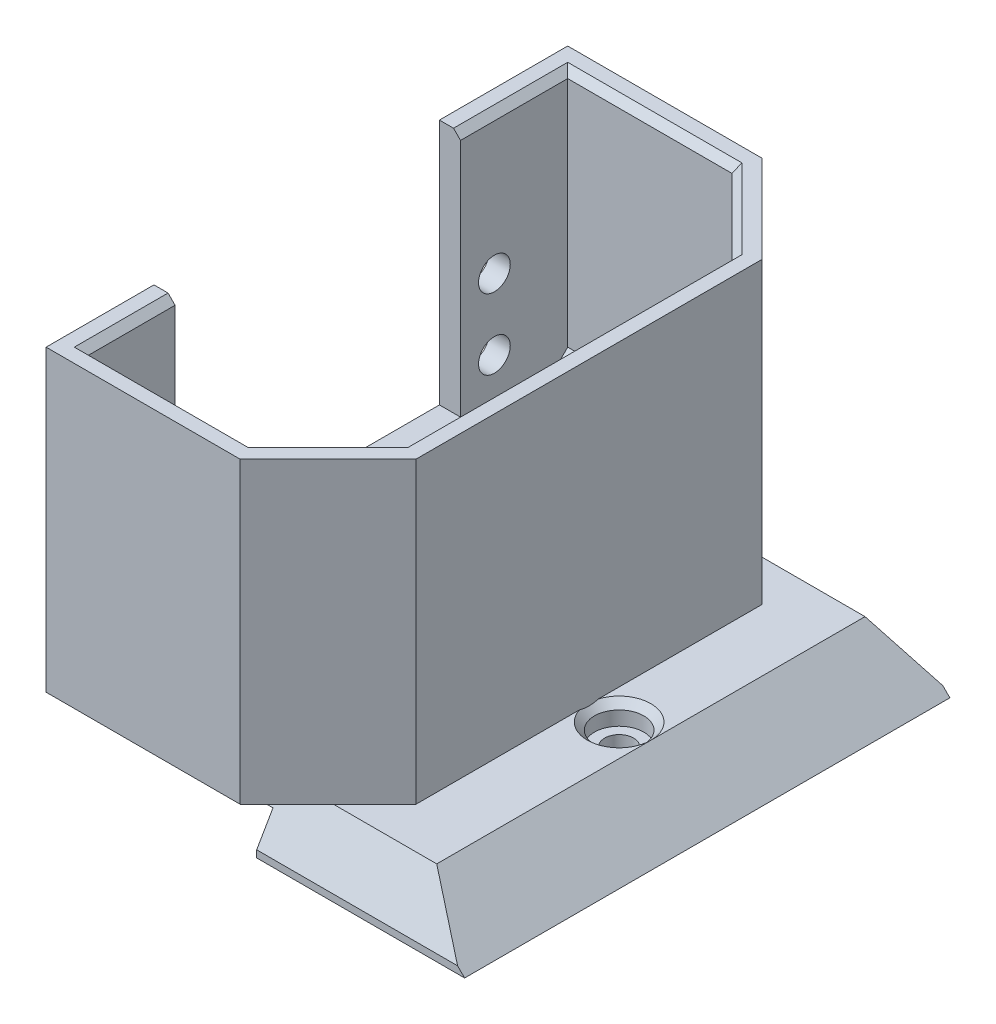
SolidWorks part; units mm, degrees
material "ABS"
ref_plane "Front Plane" through (0, 0, 0) normal (0, 0, 1) x (1, 0, 0)
ref_plane "Top Plane" through (0, 0, 0) normal (0, 1, 0) x (1, 0, 0)
ref_plane "Right Plane" through (0, 0, 0) normal (1, 0, 0) x (0, 0, -1)
sketch "Sketch1" plane through (0, 0, 0) normal (0, 1, 0) x (1, 0, 0)
  line L1 (-20, 35) -> (7.5426, 35)
  line L2 (-20, 35) -> (-20, -39)
  line L3 (-20, -39) -> (7.5426, -39)
  line L4 (20, 22.5426) -> (20, -26.5426)
  line L8 (7.5426, 35) -> (20, 22.5426)
  line L9 (7.5426, -39) -> (20, -26.5426)
  line L10 (20, 18.3) -> (3.3, 35) construction
  dimension "D4" = 20
  dimension "D5" = 3
  dimension "D3" = 16.7
  dimension "D2" = 35
  dimension "D6" = 74
  dimension "D1" = 40
extrude "Main Face Extrude" add sketch "Sketch1" along normal blind 7.4
sketch "Sketch3" plane through (0, 7.4, 0) normal (0, 1, 0) x (1, 0, 0)
  line L4 (-20, 35) -> (-20, -39)
  line L5 (-20, -39) -> (7.5426, -39)
  line L6 (20, -26.5426) -> (20, 22.5426)
  line L7 (7.5426, 35) -> (-20, 35)
  line L8 (-20, 35) -> (-20, -39)
  line L9 (-20, -39) -> (7.5426, -39)
  line L10 (20, -26.5426) -> (20, 22.5426)
  line L11 (7.5426, 35) -> (-20, 35)
  line L12 (-17, 32) -> (-17, -36)
  line L13 (-17, -36) -> (6.3, -36)
  line L14 (6.3, -36) -> (17, -25.3)
  line L15 (17, -25.3) -> (17, 21.3)
  line L16 (17, 21.3) -> (6.3, 32)
  line L17 (6.3, 32) -> (-17, 32)
  line L18 (7.5426, -39) -> (20, -26.5426)
  line L19 (7.5426, -39) -> (20, -26.5426)
  line L20 (20, 22.5426) -> (7.5426, 35)
  line L21 (20, 22.5426) -> (7.5426, 35)
  dimension "D1" = 0
  dimension "D2" = 3
extrude "Main Walls Extrude" add sketch "Sketch3" along normal blind 35
chamfer "Main Walls Lower Chamfer" distance 1 angle 45 5 edges at (-5.35, 7.4, 36) (11.65, 7.4, 30.65) (17, 7.4, 2) (11.65, 7.4, -26.65) (-5.35, 7.4, -32)
chamfer "Main Walls Entry Chamfer" distance 1 angle 45 6 edges at (-5.35, 42.4, 36) (11.65, 42.4, 30.65) (17, 42.4, 2) (11.65, 42.4, -26.65) (-17, 42.4, 2) (-5.35, 42.4, -32)
sketch "Sketch4" plane through (0, 42.4, 0) normal (0, 1, 0) x (1, 0, 0)
  line L0 (-17, 32) -> (-17, -36) construction
  line L1 (-17, 16.8) -> (-20, 16.8)
  line L2 (-17, 16.8) -> (-17, -23.7)
  line L3 (-17, -23.7) -> (-20, -23.7)
  line L4 (-20, 16.8) -> (-20, -23.7)
  line L5 (-20, 35) -> (-20, -39) construction
  point P8 (-17, -3.45)
  dimension "D1" = 40.5
  dimension "D2" = 3.45
extrude "Servo Mount Cut" cut sketch "Sketch4" against normal up to surface (35 mm away) up to face at (1.6286, 7.4, 2)
sketch "Sketch5" plane through (-20, 0, 0) normal (-1, 0, 0) x (0, 0, 1)
  line L2 (-21.6, 22.65) -> (-16.8, 22.65) construction
  line L3 (-16.8, 7.4) -> (-16.8, 42.4) construction
  line L4 (28.5, 22.65) -> (23.7, 22.65) construction
  line L5 (23.7, 7.4) -> (23.7, 42.4) construction
  line L6 (25.3, 7.4) -> (-21.3, 7.4) construction
  circle A0 centre (-21.6, 22.65) radius 2.25
  circle A1 centre (-21.6, 12.65) radius 2.25
  circle A2 centre (28.5, 22.65) radius 2.25
  circle A3 centre (28.5, 12.65) radius 2.25
  dimension "D1" = 4.5
  dimension "D2" = 10
  dimension "D3" = 50.1
  dimension "D4" = 5.25
extrude "Servo Mount Holes" cut sketch "Sketch5" against normal up to next
sketch "Sketch8" plane through (-20, 0, 0) normal (-1, 0, 0) x (0, 0, 1)
  line L0 (-28.3812, 0) -> (-32.4226, -7)
  line L1 (-35, 0) -> (39, 0) construction
  line L3 (-32.4226, -8) -> (36.4226, -8)
  line L5 (36.4226, -7) -> (32.3812, 0)
  line L6 (32.3812, 0) -> (-28.3812, 0)
  line L7 (2, -8) -> (2, 0) construction
  line L8 (-32.4226, -8) -> (-32.4226, -7)
  line L9 (36.4226, -8) -> (36.4226, -7)
  line L11 (-33, -8) -> (-32.4226, -8) construction
  line L12 (-32.4226, -7) -> (-33, -8) construction
  line L13 (36.4226, -8) -> (37, -8) construction
  line L14 (37, -8) -> (36.4226, -7) construction
  point P12 (2, 0)
  dimension "D1" = 60
  dimension "D2" = 8
  dimension "D3" = 1
  dimension "D4" = 70
extrude "Mount Dovetail" add sketch "Sketch8" against normal blind 56.8
chamfer "Mount Dovetail Chamfer" distance 8 angle 45 1 edges at (36.8, 0, 2)
sketch "Sketch9" plane through (0, -8, 0) normal (0, -1, 0) x (1, 0, 0)
  line L0 (36.8, -32.4226) -> (-20, -32.4226) construction
  line L1 (-20, 36.4226) -> (7.3, 36.4226)
  line L2 (-20, 36.4226) -> (-20, -32.4226)
  line L3 (-20, -32.4226) -> (7.3, -32.4226)
  line L4 (7.3, 36.4226) -> (7.3, -32.4226)
  dimension "D1" = 27.3
extrude "Dovetail Offset Cut" cut sketch "Sketch9" against normal blind 5
sketch "Sketch10" plane through (0, 0, 0) normal (0, 1, 0) x (1, 0, 0)
  line L0 (36.8, 32.4226) -> (36.8, -36.4226) construction
  line L1 (36.8, -2) -> (24.3, -2) construction
  circle A0 centre (24.3, -2) radius 2.05
  dimension "D2" = 4.1
  dimension "D1" = 12.5
extrude "Mount Screw Hole" cut sketch "Sketch10" against normal through all
sketch "Sketch11" plane through (0, 0, 0) normal (0, 1, 0) x (1, 0, 0)
  circle A0 centre (24.3, -2) radius 3.5
  dimension "D1" = 7
extrude "Mount Screw Countersink" cut sketch "Sketch11" against normal blind 3
chamfer "Mount Screw Countersink Chamfer" distance 1 angle 45 1 edges at (24.3, 0, 5.5)
sketch "Sketch2" plane through (0, 7.4, 0) normal (0, 1, 0) x (1, 0, 0)
  line L0 (-20, 35) -> (-20, 16.8) construction
  line L1 (-1.7, 26.5) -> (5.3, 26.5)
  line L2 (-3.7, 24.5) -> (-3.7, -11.5)
  line L3 (-1.7, -13.5) -> (5.3, -13.5)
  line L4 (7.3, 24.5) -> (7.3, -11.5)
  line L6 (-3.7, 24.5) -> (-1.7, 26.5)
  line L7 (-3.7, -11.5) -> (-1.7, -13.5)
  line L8 (5.3, -13.5) -> (7.3, -11.5)
  line L9 (5.3, 26.5) -> (7.3, 24.5)
  line L11 (1.8, 26.5) -> (1.8, -13.5) construction
  line L13 (-3.7, 6.5) -> (7.3, 6.5) construction
  line L15 (-20, -23.7) -> (-20, 16.8) construction
  point P3 (-20, -3.45)
  point P4 (1.8, 26.5)
  dimension "D1" = 11
  dimension "D2" = 40
  dimension "D3" = 21.8
  dimension "D4" = 9.95
  dimension "D5" = 2
  dimension "D6" = 2
extrude "Gear Cut" cut sketch "Sketch2" against normal through all
chamfer "Gear Entry Chamfer" distance 3 angle 45 8 edges at (6.3, 7.4, 12.5) (1.8, 7.4, 13.5) (-2.7, 7.4, 12.5) (-3.7, 7.4, -6.5) (-2.7, 7.4, -25.5) (7.3, 7.4, -6.5) (6.3, 7.4, -25.5) (1.8, 7.4, -26.5)
ref_plane "Gear Plane" through (1.8, 0, 0) normal (-1, 0, 0) x (0, 0, 1)
sketch "Reference Gear Shape" plane through (1.8, 0, 0) normal (-1, 0, 0) x (0, 0, 1)
  line L0 (-1006.3434, -4.35) -> (48993.6566, -4.35) construction
  circle A0 centre (-6.5, 17.65) radius 23
  circle A1 centre (-21.6, 22.65) radius 2.25 construction
  dimension "D1" = 46
  dimension "D2" = 15.1
  dimension "D3" = 5
  dimension "D4" = 22
equation "\"D4@Sketch1\"=\"D1@Sketch1\"/2"
